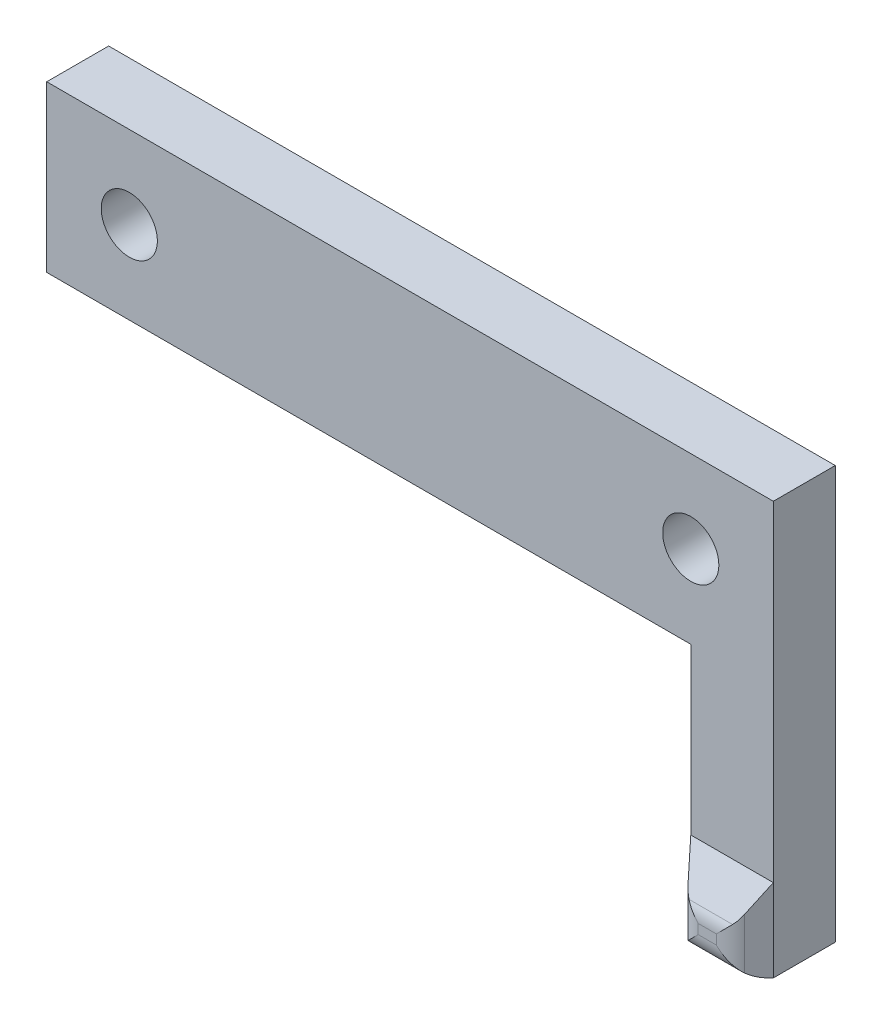
SolidWorks part; units mm, degrees
ref_plane "Front Plane" through (0, 0, 0) normal (0, 0, 1) x (1, 0, 0)
ref_plane "Top Plane" through (0, 0, 0) normal (0, 1, 0) x (1, 0, 0)
ref_plane "Right Plane" through (0, 0, 0) normal (1, 0, 0) x (0, 0, -1)
sketch "Sketch1" plane through (0, 0, 0) normal (0, 0, 1) x (1, 0, 0)
  line L0 (0, 0) -> (68, 0) construction
  line L2 (78, 10) -> (-10, 10)
  line L3 (78, 10) -> (78, -10)
  line L4 (78, -10) -> (-10, -10)
  line L5 (-10, 10) -> (-10, -10)
  line L6 (78, 10) -> (-10, -10) construction
  line L7 (78, -10) -> (-10, 10) construction
  circle A0 centre (0, 0) radius 3.4
  circle A1 centre (68, 0) radius 3.4
  point P5 (34, 0)
  dimension "D2" = 6.8
  dimension "D3" = 10
  dimension "D1" = 68
  dimension "D4" = 10
extrude "Boss-Extrude1" add sketch "Sketch1" along normal blind 7.5
sketch "Sketch2" plane through (0, -10, 0) normal (0, -1, 0) x (1, 0, 0)
  line L0 (68, 0) -> (78, 0)
  line L1 (78, 0) -> (78, 7.5)
  line L2 (-10, 7.5) -> (78, 7.5) construction
  line L3 (78, 7.5) -> (68, 7.5)
  line L4 (68, 7.5) -> (68, 0)
  line L5 (78, 7.5) -> (78, 0) construction
  point P4 (0, 0)
  point P10 (0, 0)
  point P11 (0, 0)
  point P14 (78, 3.5748)
  dimension "D1" = 10
extrude "Boss-Extrude2" add sketch "Sketch2" along normal blind 30
ref_plane "Plane1" through (0, 0, 10.5) normal (0, 0, 1) x (1, 0, 0)
sketch "Sketch3" plane through (0, 0, 10.5) normal (0, 0, 1) x (1, 0, 0)
  line L0 (78, -40) -> (68, -30) construction
  line L2 (68, -30) -> (68, -40) construction
  line L3 (73, -35) -> (73, -40) construction
  line L4 (75.5, -35) -> (70.5, -35)
  line L5 (75.5, -35) -> (75.5, -40)
  line L6 (75.5, -40) -> (70.5, -40)
  line L7 (70.5, -35) -> (70.5, -40)
  line L8 (75.5, -35) -> (70.5, -40) construction
  line L9 (75.5, -40) -> (70.5, -35) construction
  line L10 (78, -40) -> (68, -40) construction
  point P3 (-10, -30)
  point P4 (0, 0)
  point P5 (73, -37.5)
  point P12 (0, 0)
  point P13 (73, -35)
  point P18 (0, 0)
  point P19 (0, 0)
  dimension "D1" = 10
  dimension "D2" = 5
sketch "Sketch4" plane through (0, 0, 7.5) normal (0, 0, 1) x (1, 0, 0)
  line L0 (68, -30) -> (78, -40) construction
  line L2 (78, -40) -> (68, -40)
  line L3 (78, -40) -> (78, -30)
  line L4 (78, -30) -> (68, -30)
  line L5 (68, -40) -> (68, -30)
  point P4 (0, 0)
  dimension "D1" = 10
loft "Loft1" add profiles "Sketch4", "Sketch3"
fillet "Fillet1" radius 3 4 edges
